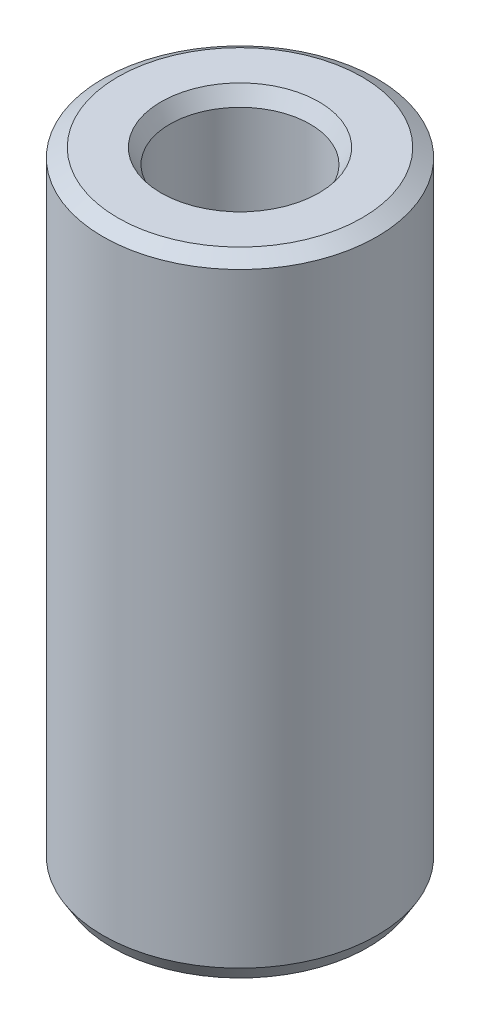
SolidWorks part; units mm, degrees
ref_plane "Front Plane" through (0, 0, 0) normal (0, 0, 1) x (1, 0, 0)
ref_plane "Top Plane" through (0, 0, 0) normal (0, 1, 0) x (1, 0, 0)
ref_plane "Right Plane" through (0, 0, 0) normal (1, 0, 0) x (0, 0, -1)
sketch "Sketch1" plane through (0, 0, 0) normal (0, 1, 0) x (1, 0, 0)
  circle A0 centre (0, 0) radius 7.5
  dimension "SLEEVE_OD" = 15
extrude "Boss-Extrude1" add sketch "Sketch1" along normal blind 34.4354
sketch "Sketch2" plane through (0, 0, 0) normal (0, 1, 0) x (1, 0, 0)
  circle A0 centre (0, 0) radius 3.8352
  dimension "BORE_D" = 7.6704
extrude "Cut-Extrude1" cut sketch "Sketch2" along normal through all
chamfer "Chamfer1" distance 0.4903 angle 58.843 4 edges at (0, 34.4354, 3.8352) (0, 0, 3.8352) (0, 0, 7.5) (0, 34.4354, 7.5) first distance on face at (0, 34.4354, 3.8352) first distance on face at (0, 0, 3.8352) first distance on face at (0, 34.4354, 7.5)
